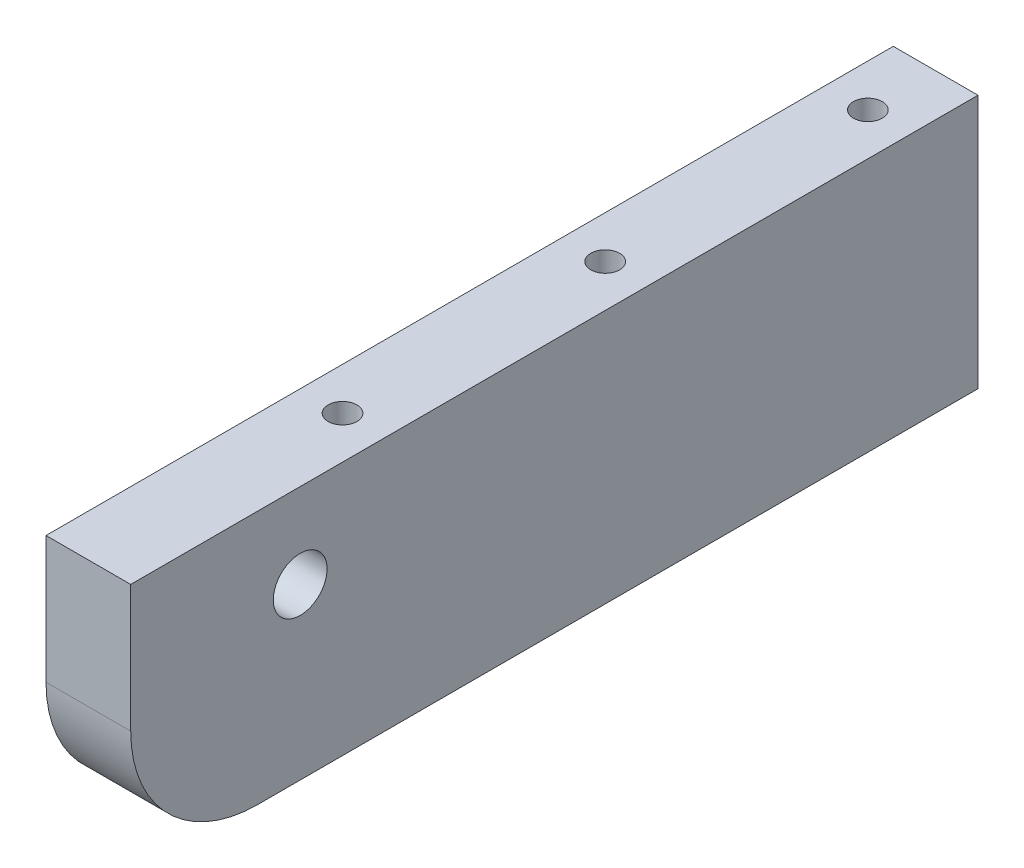
SolidWorks part; units mm, degrees
ref_plane "Front Plane" through (0, 0, 0) normal (0, 0, 1) x (1, 0, 0)
ref_plane "Top Plane" through (0, 0, 0) normal (0, 1, 0) x (1, 0, 0)
ref_plane "Right Plane" through (0, 0, 0) normal (1, 0, 0) x (0, 0, -1)
sketch "Sketch1" plane through (0, 0, 0) normal (1, 0, 0) x (0, 0, -1)
  line L1 (-50, -15) -> (50, -15)
  line L2 (-50, -15) -> (-50, 15)
  line L3 (-50, 15) -> (50, 15)
  line L4 (50, -15) -> (50, 15)
  line L5 (-50, -15) -> (50, 15) construction
  line L6 (-50, 15) -> (50, -15) construction
  circle A0 centre (-30, 5) radius 3.175
  point P0 (0, 0)
  dimension "D3" = 6.35
  dimension "D1" = 30
  dimension "D2" = 100
  dimension "D4" = 20
  dimension "D5" = 10
extrude "Boss-Extrude1" add sketch "Sketch1" along normal blind 10 contours L1 L4 L3 L2 A0 | A0 region at (0, -0.0533, -0.3201)
fillet "Fillet1" radius 15 1 edges at (5, -15, 50)
hole_wizard "CBORE for M3 SHCS" positions "Sketch4" profile "Sketch5" counterbore size "M3" standard "ANSI Metric"
sketch "Sketch4" plane through (-726.2935, 25, -1323.2827) normal (0, 1, 0) x (1, 0, 0)
  line L3 (621.2935, -1281.2827) -> (621.2935, -1365.2827) construction
  line L5 (731.2935, -1281.2827) -> (731.2935, -1343.2827) construction
  circle A0 centre (731.2935, -1281.2827) radius 2.243
  circle A1 centre (731.2935, -1343.2827) radius 2.2384
  circle A3 centre (621.2935, -1281.2827) radius 2.3325
  circle A4 centre (621.2935, -1365.2827) radius 1.7576
  circle A5 centre (621.2935, -1323.2827) radius 1.8624
  circle A6 centre (731.2935, -1312.2827) radius 2.0271
  point P1 (731.2935, -1281.2827)
  point P8 (731.2935, -1343.2827)
  point P15 (621.2935, -1281.2827)
  point P17 (621.2935, -1365.2827)
  point P19 (621.2935, -1323.2827)
  point P27 (731.2935, -1312.2827)
sketch "Sketch5" plane through (5, 25, -42) normal (1, 0, 0) x (0, 0, 1)
  line L0 (0, 0) -> (0, 24.0215)
  line L1 (0, 24.0215) -> (1.7, 23)
  line L2 (1.7, 23) -> (1.7, 3)
  line L3 (1.7, 3) -> (3.25, 3)
  line L4 (3.25, 3) -> (3.25, 0)
  line L5 (3.25, 0) -> (0, 0)
  line L6 (0, 24.0215) -> (-1.7, 23) construction
  line L7 (0, -6.35) -> (0, 107.95) construction
  dimension "Hole Dia." = 3.4
  dimension "Hole Depth" = 23
  dimension "C'Bore Dia." = 6.5
  dimension "C'Bore Depth" = 3
  dimension "Drill Angle" = 118
